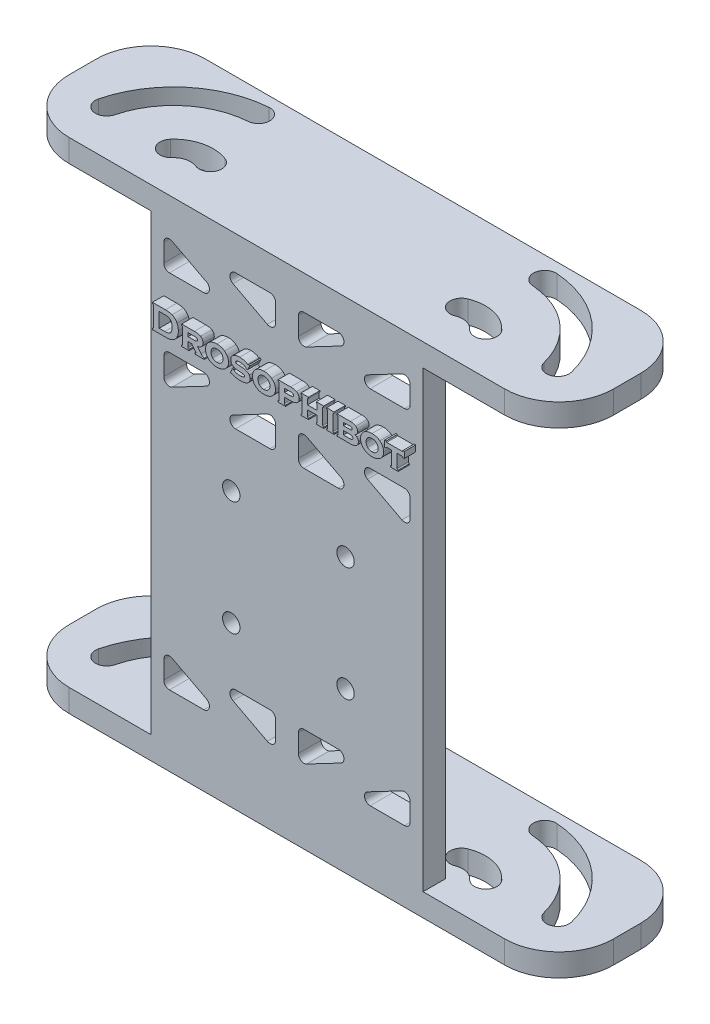
SolidWorks part; units mm, degrees
material "Polycarbonate"
ref_plane "Front Plane" through (0, 0, 0) normal (0, 0, 1) x (1, 0, 0)
ref_plane "Top Plane" through (0, 0, 0) normal (0, 1, 0) x (1, 0, 0)
ref_plane "Right Plane" through (0, 0, 0) normal (1, 0, 0) x (0, 0, -1)
sketch "Sketch1" plane through (0, 0, 0) normal (0, 1, 0) x (1, 0, 0)
  line L5 (-38.1, 9.525) -> (0, 9.525)
  line L6 (-38.1, 9.525) -> (-38.1, -9.525)
  line L13 (-38.1, -9.525) -> (38.1, -9.525)
  line L14 (38.1, 9.525) -> (38.1, -9.525)
  line L15 (-38.1, 9.525) -> (38.1, -9.525) construction
  line L16 (-38.1, -9.525) -> (38.1, 9.525) construction
  line L21 (0, 9.525) -> (38.1, 9.525)
  point P0 (0, 0)
  point P5 (0, 9.525)
  dimension "D1" = 76.2
  dimension "D2" = 19.05
extrude "Boss-Extrude1" add sketch "Sketch1" along normal blind 3.175
sketch "Sketch2" plane through (0, 3.175, 0) normal (0, 1, 0) x (1, 0, 0)
  line L0 (-38.1, -9.525) -> (38.1, -9.525) construction
  line L1 (-19.05, -9.525) -> (19.05, -9.525)
  line L2 (-19.05, -9.525) -> (-19.05, -6.35)
  line L3 (-19.05, -6.35) -> (19.05, -6.35)
  line L4 (19.05, -9.525) -> (19.05, -6.35)
  point P6 (0, -6.35)
  dimension "D1" = 38.1
  dimension "D3" = 3.175
extrude "Boss-Extrude2" add sketch "Sketch2" along normal blind 63.5
sketch "Sketch6" plane through (0, 3.175, 0) normal (0, 1, 0) x (1, 0, 0)
  line L0 (0, 34.925) -> (0, -9.5472) construction
  line L2 (-38.1, -9.525) -> (-19.05, -9.525) construction
  line L3 (-38.1, 9.525) -> (-38.1, -9.525) construction
  arc A0 (-20.0369, 6.5336) -> (-31.5752, -3.175) centre (-19.05, -6.35) ccw construction
  arc A1 (-20.1581, 8.1164) -> (-33.114, -2.7849) centre (-19.05, -6.35) ccw
  arc A2 (-19.9156, 4.9507) -> (-30.0363, -3.5651) centre (-19.05, -6.35) ccw
  arc A3 (-19.9156, 4.9507) -> (-20.1581, 8.1164) centre (-20.0369, 6.5336) ccw
  arc A4 (-33.114, -2.7849) -> (-30.0363, -3.5651) centre (-31.5752, -3.175) ccw
  arc A5 (-17.5716, -2.6669) -> (-22.0054, -3.7011) centre (-19.05, -6.35) ccw construction
  arc A6 (-16.9803, -1.1936) -> (-23.1875, -2.6415) centre (-19.05, -6.35) ccw
  arc A7 (-18.163, -4.1401) -> (-20.8232, -4.7607) centre (-19.05, -6.35) ccw
  arc A8 (-18.163, -4.1401) -> (-16.9803, -1.1936) centre (-17.5716, -2.6669) ccw
  arc A9 (-23.1875, -2.6415) -> (-20.8232, -4.7607) centre (-22.0054, -3.7011) ccw
  arc A10 (17.5716, -2.6669) -> (22.0054, -3.7011) centre (19.05, -6.35) cw construction
  arc A15 (16.9803, -1.1936) -> (23.1875, -2.6415) centre (19.05, -6.35) cw
  arc A20 (18.163, -4.1401) -> (20.8232, -4.7607) centre (19.05, -6.35) cw
  arc A21 (18.163, -4.1401) -> (16.9803, -1.1936) centre (17.5716, -2.6669) cw
  arc A22 (23.1875, -2.6415) -> (20.8232, -4.7607) centre (22.0054, -3.7011) cw
  arc A23 (20.0369, 6.5336) -> (31.5752, -3.175) centre (19.05, -6.35) cw construction
  arc A24 (20.1581, 8.1164) -> (33.114, -2.7849) centre (19.05, -6.35) cw
  arc A25 (19.9156, 4.9507) -> (30.0363, -3.5651) centre (19.05, -6.35) cw
  arc A26 (19.9156, 4.9507) -> (20.1581, 8.1164) centre (20.0369, 6.5336) cw
  arc A27 (33.114, -2.7849) -> (30.0363, -3.5651) centre (31.5752, -3.175) cw
  point P5 (-27.3691, 3.537)
  point P10 (-19.9516, -2.485)
  point P28 (19.9516, -2.485)
  point P37 (27.3691, 3.537)
  dimension "D3" = 3.175
  dimension "D5" = 3.175
  dimension "D1" = 18.0631
  dimension "D2" = 16.0586
  dimension "D4" = 6.35
  dimension "D6" = 6.8581
  dimension "D7" = 20.5284
  dimension "D8" = 16.0946
extrude "Cut-Extrude1" cut sketch "Sketch6" against normal through all
fillet "Fillet1" radius 7.62 4 edges at (-38.1, 1.5875, -9.525) (38.1, 1.5875, -9.525) (38.1, 1.5875, 9.525) (-38.1, 1.5875, 9.525)
hole_wizard "#2 Clearance Hole2" positions "Sketch7" profile "Sketch8" hole size "#2" standard "ANSI Inch" end condition up to next
sketch "Sketch7" plane through (0, 0, 6.35) normal (0, 0, -1) x (-1, 0, 0)
  point P3 (7.7997, 38.35)
  point P16 (-8.2003, 22.35)
  point P19 (7.7997, 22.35)
  point P26 (-8.2003, 38.35)
sketch "Sketch8" plane through (-7.7997, 38.35, 6.35) normal (1, 0, 0) x (0, 1, 0)
  line L0 (0, 0) -> (0, 3.175)
  line L1 (0, 3.175) -> (1.2192, 3.175)
  line L2 (1.2192, 3.175) -> (1.2192, 0)
  line L5 (1.2192, 0) -> (0, 0)
  line L11 (0, -6.35) -> (0, 107.95) construction
  dimension "Thru Hole Dia." = 2.4384
  dimension "Thru Hole Depth" = 3.175
ref_plane "Plane1" through (0, 34.925, 0) normal (0, 1, 0) x (1, 0, 0)
mirror "Mirror1" about plane through (0, 34.925, 0) normal (0, 1, 0) of "Fillet1", "Cut-Extrude1", "Boss-Extrude1"
sketch "Sketch9" plane through (0, 0, 9.525) normal (0, 0, 1) x (1, 0, 0)
  line L0 (19.05, 66.675) -> (-19.05, 66.675) construction
  line L1 (19.05, 66.675) -> (-19.05, 66.675) construction
  line L2 (-19.05, 41.275) -> (19.05, 41.275) construction
  line L3 (-19.05, 66.675) -> (-19.05, 3.175) construction
  line L4 (19.05, 66.675) -> (19.05, 3.175) construction
  line L5 (-19.05, 66.675) -> (-19.05, 41.275) construction
  line L6 (19.05, 66.675) -> (19.05, 41.275) construction
  line L7 (-19.05, 53.975) -> (19.05, 53.975) construction
  text T0 "<b>Drosophibot</b>" font "Copperplate Gothic Bold" height in points 16
  dimension "D1" = 25.4
extrude "Boss-Extrude3" add sketch "Sketch9" along normal blind 1.5875
sketch "Sketch10" plane through (0, 0, 9.525) normal (0, 0, 1) x (1, 0, 0)
  line L0 (-15.4315, 53.975) -> (-17.2451, 53.975) construction
  line L1 (-15.4315, 53.975) -> (-17.2451, 53.975) construction
  line L2 (-17.2451, 57.2835) -> (-15.4315, 57.2835) construction
  line L3 (-17.2451, 57.2835) -> (-15.4315, 57.2835) construction
  line L4 (-19.05, 52.3875) -> (19.05, 52.3875) construction
  line L5 (-19.05, 66.675) -> (-19.05, 3.175) construction
  line L6 (19.05, 66.675) -> (19.05, 3.175) construction
  line L7 (-19.05, 58.871) -> (0, 58.871) construction
  line L8 (-19.05, 66.675) -> (0, 66.675) construction
  line L9 (-17.2451, 63.7747) -> (-17.2451, 61.2523)
  line L10 (-19.05, 55.6293) -> (19.05, 55.6293) construction
  line L11 (-19.05, 58.871) -> (-19.05, 52.3875) construction
  line L12 (-16.4513, 60.4585) -> (-11.6432, 60.4585)
  line L13 (-11.2745, 61.9552) -> (-16.0826, 64.4776)
  line L14 (-7.1893, 65.0875) -> (-2.3813, 65.0875)
  line L15 (-1.5875, 64.2937) -> (-1.5875, 61.7713)
  line L16 (-2.75, 61.0684) -> (-7.5581, 63.5909)
  line L17 (0, 55.6293) -> (0, 66.675) construction
  line L18 (1.5875, 64.2937) -> (1.5875, 61.7713)
  line L19 (7.1893, 65.0875) -> (2.3812, 65.0875)
  line L20 (2.75, 61.0684) -> (7.5581, 63.5909)
  line L21 (16.4513, 60.4585) -> (11.6432, 60.4585)
  line L22 (17.2451, 63.7747) -> (17.2451, 61.2523)
  line L23 (11.2745, 61.9552) -> (16.0826, 64.4776)
  line L24 (17.2451, 47.4838) -> (17.2451, 50.0063)
  line L25 (11.2745, 49.3034) -> (16.0826, 46.7809)
  line L26 (16.4513, 50.8) -> (11.6432, 50.8)
  line L27 (7.1893, 46.171) -> (2.3812, 46.171)
  line L28 (2.75, 50.1901) -> (7.5581, 47.6677)
  line L29 (1.5875, 46.9648) -> (1.5875, 49.4872)
  line L30 (-1.5875, 46.9648) -> (-1.5875, 49.4872)
  line L31 (-7.1893, 46.171) -> (-2.3813, 46.171)
  line L32 (-2.75, 50.1901) -> (-7.5581, 47.6677)
  line L33 (-16.4513, 50.8) -> (-11.6432, 50.8)
  line L34 (-17.2451, 47.4838) -> (-17.2451, 50.0063)
  line L35 (-11.2745, 49.3034) -> (-16.0826, 46.7809)
  line L36 (-7.7997, 38.35) -> (-7.7997, 22.35) construction
  line L37 (-19.05, 30.35) -> (19.05, 30.35) construction
  line L38 (11.2745, 11.3966) -> (16.0826, 13.9191)
  line L39 (16.4513, 9.9) -> (11.6432, 9.9)
  line L40 (17.2451, 13.2162) -> (17.2451, 10.6938)
  line L41 (2.75, 10.5099) -> (7.5581, 13.0323)
  line L42 (1.5875, 13.7352) -> (1.5875, 11.2128)
  line L43 (7.1893, 14.529) -> (2.3812, 14.529)
  line L44 (-7.1893, 14.529) -> (-2.3813, 14.529)
  line L45 (-2.75, 10.5099) -> (-7.5581, 13.0323)
  line L46 (-1.5875, 13.7352) -> (-1.5875, 11.2128)
  line L47 (-17.2451, 13.2162) -> (-17.2451, 10.6938)
  line L48 (-11.2745, 11.3966) -> (-16.0826, 13.9191)
  line L49 (-16.4513, 9.9) -> (-11.6432, 9.9)
  arc A0 (17.2451, 47.4838) -> (16.0826, 46.7809) centre (16.4513, 47.4838) cw
  arc A1 (17.2451, 50.0063) -> (16.4513, 50.8) centre (16.4513, 50.0063) ccw
  arc A2 (11.2745, 49.3034) -> (11.6432, 50.8) centre (11.6432, 50.0063) cw
  arc A3 (7.1893, 46.171) -> (7.5581, 47.6677) centre (7.1893, 46.9648) ccw
  arc A4 (2.75, 50.1901) -> (1.5875, 49.4872) centre (2.3812, 49.4872) ccw
  arc A5 (2.3812, 46.171) -> (1.5875, 46.9648) centre (2.3812, 46.9648) cw
  arc A6 (-7.1893, 46.171) -> (-7.5581, 47.6677) centre (-7.1893, 46.9648) cw
  arc A7 (-1.5875, 46.9648) -> (-2.3813, 46.171) centre (-2.3813, 46.9648) cw
  arc A8 (-1.5875, 49.4872) -> (-2.75, 50.1901) centre (-2.3813, 49.4872) ccw
  arc A9 (-11.6432, 50.8) -> (-11.2745, 49.3034) centre (-11.6432, 50.0063) cw
  arc A10 (-17.2451, 47.4838) -> (-16.0826, 46.7809) centre (-16.4513, 47.4838) ccw
  arc A11 (-16.4513, 50.8) -> (-17.2451, 50.0063) centre (-16.4513, 50.0063) ccw
  arc A12 (11.6432, 60.4585) -> (11.2745, 61.9552) centre (11.6432, 61.2523) cw
  arc A13 (16.4513, 60.4585) -> (17.2451, 61.2523) centre (16.4513, 61.2523) ccw
  arc A14 (17.2451, 63.7747) -> (16.0826, 64.4776) centre (16.4513, 63.7747) ccw
  arc A15 (7.1893, 65.0875) -> (7.5581, 63.5909) centre (7.1893, 64.2938) cw
  arc A16 (1.5875, 64.2937) -> (2.3812, 65.0875) centre (2.3812, 64.2938) cw
  arc A17 (1.5875, 61.7713) -> (2.75, 61.0684) centre (2.3812, 61.7713) ccw
  arc A18 (-1.5875, 61.7713) -> (-2.75, 61.0684) centre (-2.3813, 61.7713) cw
  arc A19 (-2.3813, 65.0875) -> (-1.5875, 64.2937) centre (-2.3812, 64.2938) cw
  arc A20 (-7.1893, 65.0875) -> (-7.5581, 63.5909) centre (-7.1893, 64.2938) ccw
  arc A21 (-11.6432, 60.4585) -> (-11.2745, 61.9552) centre (-11.6432, 61.2523) ccw
  arc A22 (-17.2451, 61.2523) -> (-16.4513, 60.4585) centre (-16.4513, 61.2523) ccw
  arc A23 (-17.2451, 63.7747) -> (-16.0826, 64.4776) centre (-16.4513, 63.7747) cw
  arc A25 (11.2745, 11.3966) -> (11.6432, 9.9) centre (11.6432, 10.6938) ccw
  arc A26 (17.2451, 13.2162) -> (16.0826, 13.9191) centre (16.4513, 13.2162) ccw
  arc A27 (17.2451, 10.6938) -> (16.4513, 9.9) centre (16.4513, 10.6938) cw
  arc A28 (2.75, 10.5099) -> (1.5875, 11.2128) centre (2.3812, 11.2128) cw
  arc A29 (7.1893, 14.529) -> (7.5581, 13.0323) centre (7.1893, 13.7352) cw
  arc A30 (2.3812, 14.529) -> (1.5875, 13.7352) centre (2.3812, 13.7352) ccw
  arc A31 (-7.1893, 14.529) -> (-7.5581, 13.0323) centre (-7.1893, 13.7352) ccw
  arc A32 (-1.5875, 13.7352) -> (-2.3813, 14.529) centre (-2.3813, 13.7352) ccw
  arc A33 (-1.5875, 11.2128) -> (-2.75, 10.5099) centre (-2.3813, 11.2128) cw
  arc A34 (-17.2451, 13.2162) -> (-16.0826, 13.9191) centre (-16.4513, 13.2162) cw
  arc A35 (-11.6432, 9.9) -> (-11.2745, 11.3966) centre (-11.6432, 10.6938) ccw
  arc A36 (-16.4513, 9.9) -> (-17.2451, 10.6938) centre (-16.4513, 10.6938) cw
  point P21 (-19.05, 55.6293)
  point P26 (-7.7997, 30.35)
  point P47 (17.2451, 46.171)
  point P50 (17.2451, 50.8)
  point P53 (8.4217, 50.8)
  point P56 (10.4109, 46.171)
  point P59 (1.5875, 50.8)
  point P62 (1.5875, 46.171)
  point P65 (-10.4109, 46.171)
  point P68 (-1.5875, 46.171)
  point P71 (-1.5875, 50.8)
  point P74 (-8.4217, 50.8)
  point P77 (-17.2451, 46.171)
  point P80 (-17.2451, 50.8)
  point P83 (8.4217, 60.4585)
  point P86 (17.2451, 60.4585)
  point P89 (17.2451, 65.0875)
  point P92 (10.4109, 65.0875)
  point P95 (1.5875, 65.0875)
  point P98 (1.5875, 60.4585)
  point P101 (-1.5875, 60.4585)
  point P104 (-1.5875, 65.0875)
  point P107 (-10.4109, 65.0875)
  point P110 (-8.4217, 60.4585)
  point P113 (-17.2451, 60.4585)
  point P116 (-17.2451, 65.0875)
  dimension "D3" = 3.175
  dimension "D7" = 0.7937
  dimension "D1" = 1.5875
  dimension "D2" = 1.5875
  dimension "D4" = 1.5875
  dimension "D5" = 1.5875
  dimension "D6" = 1.5875
extrude "Cut-Extrude2" cut sketch "Sketch10" against normal up to surface (3.175 mm away) up to face at (-9.0189, 38.35, 6.35)
